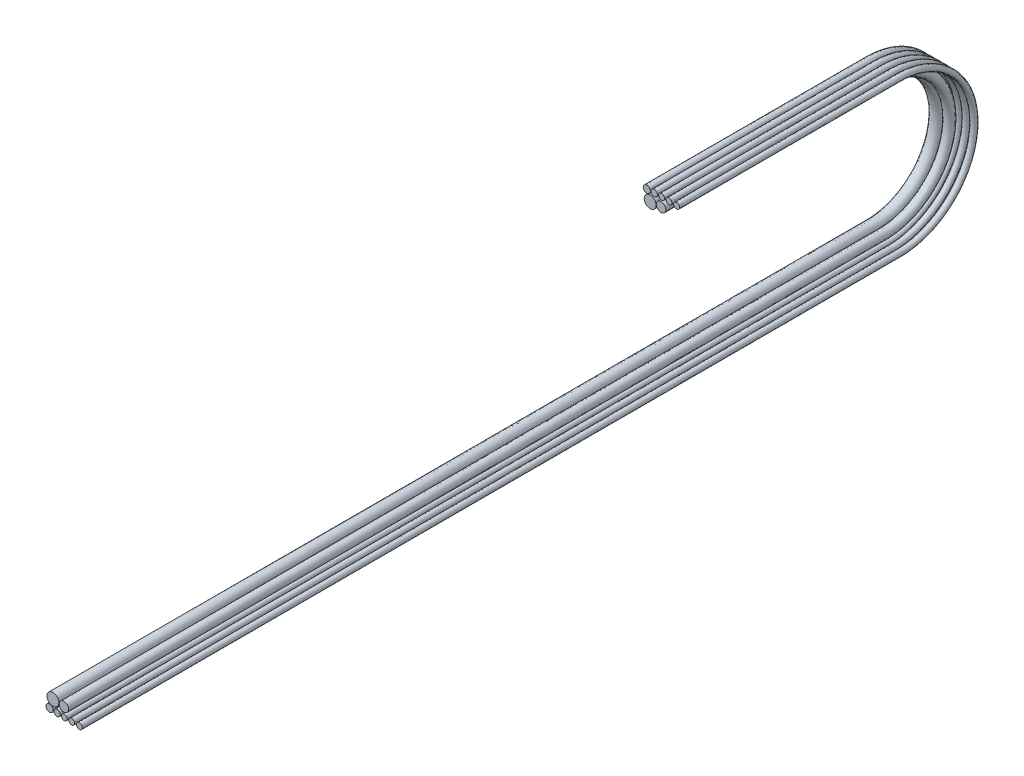
SolidWorks part; units mm, degrees
ref_plane "Front Plane" through (0, 0, 0) normal (0, 0, 1) x (1, 0, 0)
ref_plane "Top Plane" through (0, 0, 0) normal (0, 1, 0) x (1, 0, 0)
ref_plane "Right Plane" through (0, 0, 0) normal (1, 0, 0) x (0, 0, -1)
sketch "Sketch1" plane through (0, 0, 0) normal (0, 0, 1) x (1, 0, 0)
  line L1 (18.5, 18) -> (-18.5, 18) construction
  line L2 (18.5, 18) -> (18.5, 0) construction
  line L3 (18.5, 0) -> (-18.5, 0) construction
  line L4 (-18.5, 18) -> (-18.5, 0) construction
  circle A0 centre (-16.1, 2.4) radius 2.4
  circle A2 centre (-11.0983, 2.15) radius 2.15
  circle A5 centre (-6.1615, 1.95) radius 1.95
  circle A6 centre (-1.1864, 2) radius 2
  circle A7 centre (-13.8535, 8.6823) radius 4
  circle A8 centre (-6.4473, 8.0498) radius 3.15
  circle A9 centre (3.9878, 2) radius 2
  dimension "D3" = 4.8
  dimension "D4" = 4.3
  dimension "D5" = 3.9
  dimension "D6" = 4
  dimension "D7" = 8
  dimension "D8" = 6.3
  dimension "D1" = 37
  dimension "D2" = 18
sketch "Sketch2" plane through (0, 0, 0) normal (1, 0, 0) x (0, 0, -1)
  spline S1 degree 3 poles (-999.9985, 9.7) (-482.8877, 9.7) (34.2951, 9.7) (551.5499, 9.7) (551.7658, 9.702) (551.9098, 9.7038) (551.9818, 9.7048) (636.4464, 10.963) (636.4464, 95.437) (551.9818, 96.6952) (551.9098, 96.6962) (551.7658, 96.698) (551.5499, 96.7) (168.4043, 96.7) (-214.6693, 96.7) (-597.6709, 96.7) knots -1.268025 -1.268025 -1.268025 -1.268025 0.699106 0.69938 0.699654 0.699928 0.699928 0.699928 0.810234 0.810234 0.810234 0.810508 0.810781 0.811055 2.268024 2.268024 2.268024 2.268024 weights 1 1 1 1 1 1 1 0.343263 0.343263 1 1 1 1 1 1 1 only from (0, 9.7) to (402.3271, 96.7) construction
  spline S2 degree 3 poles (0, 9.7) (183.778, 9.7) (367.6279, 9.7) (551.5499, 9.7) (551.7658, 9.702) (551.9098, 9.7038) (551.9818, 9.7048) (636.4464, 10.963) (636.4464, 95.437) (551.9818, 96.6952) (551.9098, 96.6962) (551.7658, 96.698) (551.5499, 96.7) (501.7369, 96.7) (451.996, 96.7) (402.3271, 96.7) knots 0 0 0 0 0.699106 0.69938 0.699654 0.699928 0.699928 0.699928 0.810234 0.810234 0.810234 0.810508 0.810781 0.811055 1 1 1 1 weights 1 1 1 1 1 1 1 0.343263 0.343263 1 1 1 1 1 1 1
sweep "Sweep1" add profiles "Sketch1" path "Sketch2"
